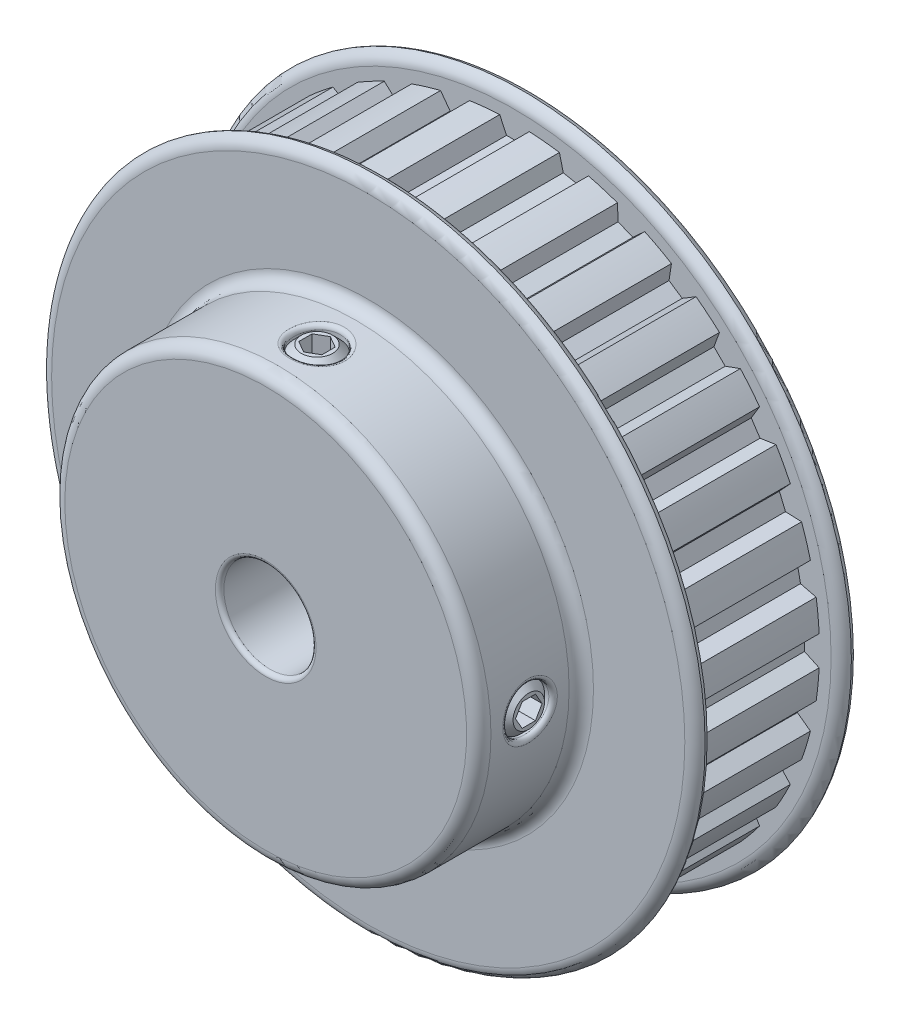
SolidWorks part; units mm, degrees
ref_plane "Front Plane" through (0, 0, 0) normal (0, 0, 1) x (1, 0, 0)
ref_plane "Top Plane" through (0, 0, 0) normal (0, 1, 0) x (1, 0, 0)
ref_plane "Right Plane" through (0, 0, 0) normal (1, 0, 0) x (0, 0, -1)
sketch "Sketch1" plane through (0, 0, 0) normal (0, 0, 1) x (1, 0, 0)
  line L0 (-1.2827, 26.4496) -> (-0.6905, 25.1796)
  line L1 (-0.6905, 25.1796) -> (0.6905, 25.1796)
  line L2 (0.6905, 25.1796) -> (1.2827, 26.4496)
  line L3 (-1.2827, 26.4496) -> (1.2827, 26.4496)
  line L4 (0, 0) -> (0, 25.1796) construction
  line L5 (0, 25.1796) -> (0, 27.4656) construction
  circle A0 centre (0, 0) radius 25.85 construction
  circle A1 centre (0, 0) radius 28.5 construction
  circle A2 centre (0, 0) radius 26.4807 construction
  point P6 (0, 26.4496)
  point P11 (0, 25.85)
  point P13 (0, 28.5)
  point P14 (0, 26.4807)
  dimension "Pitch Diameter" = 51.7
  dimension "OD" = 57
  dimension "D5" = 50
  dimension "D6" = 2.5654
  dimension "D4" = 1.27
  dimension "D3" = 2.286
  dimension "D2" = 1.6156
sketch "Sketch2" plane through (0, 0, 0) normal (1, 0, 0) x (0, 0, -1)
  line L0 (-11.55, 4) -> (11.55, 4) construction
  line L1 (-11.55, 4) -> (-11.55, 18.5) construction
  line L2 (-11.55, 18.5) -> (-2.65, 18.5) construction
  line L3 (-2.65, 18.5) -> (-2.65, 28.5) construction
  line L4 (-2.65, 28.5) -> (-1.15, 28.5) construction
  line L5 (-1.15, 28.5) -> (-1.15, 26.4807) construction
  line L6 (-1.15, 26.4807) -> (10.05, 26.4807) construction
  line L7 (10.05, 26.4807) -> (10.05, 28.5) construction
  line L8 (10.05, 28.5) -> (11.55, 28.5) construction
  line L9 (11.55, 28.5) -> (11.55, 4) construction
  line L10 (-11.55, 0) -> (11.55, 0) construction
  line L13 (-2.65, 28.5) -> (-1.9, 28.5) construction
  line L14 (-1.15, 27.4904) -> (-1.15, 26.4807) construction
  line L15 (10.05, 26.4807) -> (10.05, 27.4904) construction
  line L16 (10.8, 28.5) -> (11.55, 28.5) construction
  arc A0 (-1.15, 27.4904) -> (-1.9, 28.5) centre (-2.2046, 27.4904) ccw construction
  arc A1 (10.05, 27.4904) -> (10.8, 28.5) centre (11.1046, 27.4904) cw construction
  point P12 (-1.15, 27.4904)
  point P14 (-1.9, 28.5)
  point P20 (10.05, 27.4904)
  point P21 (10.8, 28.5)
  point P25 (10.05, 0)
  point P26 (-1.15, 0)
  dimension "Overall Width" = 23.1
  dimension "Outside Width" = 14.2
  dimension "Inside Width" = 11.2
  dimension "Hub Diameter" = 37
  dimension "For Shaft Diameter" = 8
sketch "Sketch7" plane through (0, 0, 0) normal (1, 0, 0) x (0, 0, -1)
  line L0 (-11.55, 4) -> (-11.55, 18.5) construction
  line L1 (-11.55, 18.5) -> (-2.65, 18.5) construction
  line L2 (-2.65, 18.5) -> (-2.65, 28.5) construction
  line L3 (-2.65, 28.5) -> (-1.9, 28.5) construction
  line L4 (-1.15, 27.4904) -> (-1.15, 26.4807) construction
  line L5 (-1.15, 26.4807) -> (10.05, 26.4807) construction
  line L6 (10.05, 26.4807) -> (10.05, 27.4904) construction
  line L7 (10.8, 28.5) -> (11.55, 28.5) construction
  line L8 (11.55, 28.5) -> (11.55, 4) construction
  line L9 (-11.55, 4) -> (11.55, 4) construction
  line L10 (-11.55, 4) -> (-11.55, 18.5)
  line L11 (-11.55, 18.5) -> (-2.65, 18.5)
  line L12 (-2.65, 18.5) -> (-2.65, 28.5)
  line L13 (-2.65, 28.5) -> (-1.9, 28.5)
  line L14 (-1.15, 27.4904) -> (-1.15, 26.4807)
  line L15 (-1.15, 26.4807) -> (10.05, 26.4807)
  line L16 (10.05, 26.4807) -> (10.05, 27.4904)
  line L17 (10.8, 28.5) -> (11.55, 28.5)
  line L18 (11.55, 28.5) -> (11.55, 4)
  line L19 (-11.55, 4) -> (11.55, 4)
  arc A0 (-1.15, 27.4904) -> (-1.9, 28.5) centre (-2.2046, 27.4904) ccw construction
  arc A1 (10.8, 28.5) -> (10.05, 27.4904) centre (11.1046, 27.4904) ccw construction
  arc A2 (-1.15, 27.4904) -> (-1.9, 28.5) centre (-2.2046, 27.4904) ccw
  arc A3 (10.8, 28.5) -> (10.05, 27.4904) centre (11.1046, 27.4904) ccw
revolve "Revolve1" add sketch "Sketch7" angle 360 about L10
sketch "Sketch3" plane through (0, 0, 0) normal (0, 0, 1) x (1, 0, 0)
  line L0 (-0.6905, 25.1796) -> (0.6905, 25.1796) construction
  line L1 (0.6905, 25.1796) -> (1.2827, 26.4496) construction
  line L2 (-1.2827, 26.4496) -> (-0.6905, 25.1796) construction
  line L3 (-0.6905, 25.1796) -> (0.6905, 25.1796)
  line L4 (0.6905, 25.1796) -> (1.2827, 26.4496)
  line L5 (-1.2827, 26.4496) -> (-0.6905, 25.1796)
  arc A1 (1.2827, 26.4496) -> (-1.2827, 26.4496) centre (0, 0) ccw
  circle A2 centre (0, 0) radius 26.4807 construction
extrude "Cut-Extrude1" cut sketch "Sketch3" against normal up to vertex (10.05 mm away) from vertex up to point (0, 26.4807, -10.05) starting at point (0, 26.4807, 1.15)
pattern_circular "CirPattern1" count 32 over 360 about axis through (0, 0, 11.55) along (0, 0, -1) of "Cut-Extrude1" reverse direction yes
sketch "Sketch4" plane through (0, 0, 0) normal (0, 1, 0) x (1, 0, 0)
  line L0 (0, -2.65) -> (0, -11.55) construction
  line L3 (0, -11.55) -> (0, 11.55) construction
  line L4 (-18.5, -2.65) -> (18.5, -2.65) construction
  line L5 (-18.5, -11.55) -> (18.5, -11.55) construction
  circle A0 centre (0, -7.1) radius 2
  dimension "D1" = 4
extrude "Cut-Extrude2" cut sketch "Sketch4" along normal through all
ref_plane "Plane1" through (0, 0, 7.1) normal (0, 0, 1) x (1, 0, 0)
sketch "Sketch5" plane through (0, 0, 7.1) normal (0, 0, 1) x (1, 0, 0)
  line L0 (0, 0) -> (0, 18.5) construction
  line L1 (-2, 18.3916) -> (-2, 3.4641) construction
  line L2 (-2, 18.3916) -> (-2, 3.4641) construction
  line L3 (0, 18.3916) -> (0, 4)
  line L4 (0, 4) -> (-1.365, 4)
  line L5 (-2, 17.7566) -> (-2, 4.635)
  line L6 (-1.365, 18.3916) -> (0, 18.3916)
  line L7 (-2, 17.7566) -> (-1.365, 18.3916)
  line L8 (-2, 4.635) -> (-1.365, 4)
  line L9 (0, 28.5) -> (0, 4) construction
  line L10 (0, 4) -> (0, 18.5) construction
  point P13 (-2, 4)
  point P15 (-2, 18.3916)
revolve "Revolve2" add sketch "Sketch5" angle 360 mid plane about L0
sketch "Sketch6" plane through (0, 18.3916, 0) normal (0, -1, 0) x (-1, 0, 0)
  line L1 (0, -5.9453) -> (-1, -6.5226)
  line L2 (-1, -6.5226) -> (-1, -7.6774)
  line L3 (-1, -7.6774) -> (0, -8.2547)
  line L4 (0, -8.2547) -> (1, -7.6774)
  line L5 (1, -7.6774) -> (1, -6.5226)
  line L6 (1, -6.5226) -> (0, -5.9453)
  circle A0 centre (0, -7.1) radius 1 construction
  dimension "D1" = 2
extrude "Cut-Extrude3" cut sketch "Sketch6" along normal blind 1.5
pattern_circular "CirPattern2" count 2 every 90 about axis through (0, 0, 11.55) along (0, 0, -1) of "Cut-Extrude2", "Revolve2", "Cut-Extrude3"
fillet "Fillet1" radius 1.0571 4 edges at (28.5, 0, -11.55) (28.5, 0, 2.65) (18.5, 0, 2.65) (18.5, 0, 11.55)
fillet "Fillet2" radius 0.37 4 edges at (4, 0, 11.55) (18.4946, -0.4469, 9.0494) (0.4469, 18.4946, 9.0494) (4, 0, -11.55)
equation "\"D1@Sketch4\" = \"For Shaft Diameter@Sketch2\"/2"
equation "\"D1@Sketch6\" = \"D1@Sketch4\"/2"
equation "\"D1@Cut-Extrude3\" = \"D1@Sketch6\"*.75"
equation "\"D1@Fillet1\"=\"Hub Diameter@Sketch2\" / 35"
equation "\"D2@Sketch1\"=\"Pitch Diameter@Sketch1\"/32"
equation "\"D1@Fillet2\"=\"Hub Diameter@Sketch2\"*.01"
